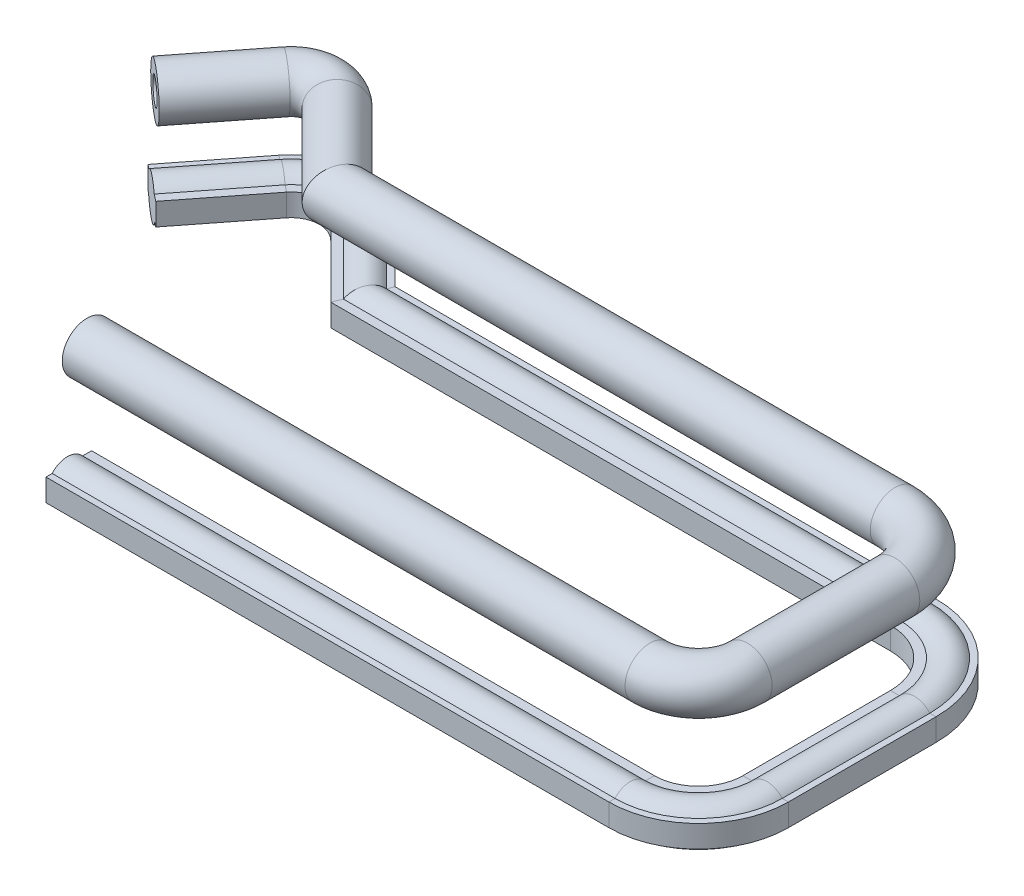
SolidWorks part; units mm, degrees
note: The reader was unsure of these and kept them because the rebuilt part matched: shared geometry of "Path<2>".
ref_plane "Front Plane" through (0, 0, 0) normal (0, 0, 1) x (1, 0, 0)
ref_plane "Top Plane" through (0, 0, 0) normal (0, 1, 0) x (1, 0, 0)
ref_plane "Right Plane" through (0, 0, 0) normal (1, 0, 0) x (0, 0, -1)
sketch "Path" plane through (0, 0, 0) normal (0, 1, 0) x (1, 0, 0)
  line L0 (-106.1844, 58.4057) -> (115.2079, 58.4057)
  line L1 (146.7184, 26.8951) -> (146.7184, -32.4429)
  line L2 (120.1186, -59.0427) -> (-106.1844, -59.0427)
  line L3 (-106.1844, 58.4057) -> (-134.0706, 86.2919)
  line L4 (-163.9647, 84.4736) -> (-187.0623, 54.9508)
  arc A0 (115.2079, 58.4057) -> (146.7184, 26.8951) centre (115.2079, 26.8951) cw
  arc A1 (146.7184, -32.4429) -> (120.1186, -59.0427) centre (120.1186, -32.4429) cw
  arc A2 (-134.0706, 86.2919) -> (-163.9647, 84.4736) centre (-148.2127, 72.1498) ccw
  dimension "D1" = 20
sketch "profile circle" plane through (0, 0, 0) normal (1, 0, 0) x (0, 0, -1)
  line L0 (-32.4429, 0) -> (-59.0427, 0) construction
  line L2 (-68.55, 5.275) -> (-66.0632, 5.275)
  line L3 (-68.55, 5.275) -> (-68.55, -3.6793)
  line L4 (-68.55, -3.6793) -> (-67.1378, -3.6793)
  line L6 (-53.8405, 5.275) -> (-50.2317, 5.275)
  line L8 (-52.766, -3.6793) -> (-50.2317, -3.6793)
  line L9 (-50.2317, 5.275) -> (-50.2317, -3.6793)
  arc A0 (-67.1378, -3.6793) -> (-52.766, -3.6793) centre (-59.9519, 0) ccw
  arc A1 (-53.8405, 5.275) -> (-66.0632, 5.275) centre (-59.9519, 0) ccw
sweep "Sweep1" add profiles "profile circle" path "Path"
sketch "circle out path" plane through (0, 0, 0) normal (1, 0, 0) x (0, 0, -1)
  circle A0 centre (-52.0639, 42.4001) radius 7.463
sweep "Sweep-Thin1" add profiles "circle out path" path "Path<2>" parameters "D1"=5
sketch "Path<2>" plane through (0, 0, 0) normal (0, 1, 0) x (1, 0, 0) same geometry as "Path"
